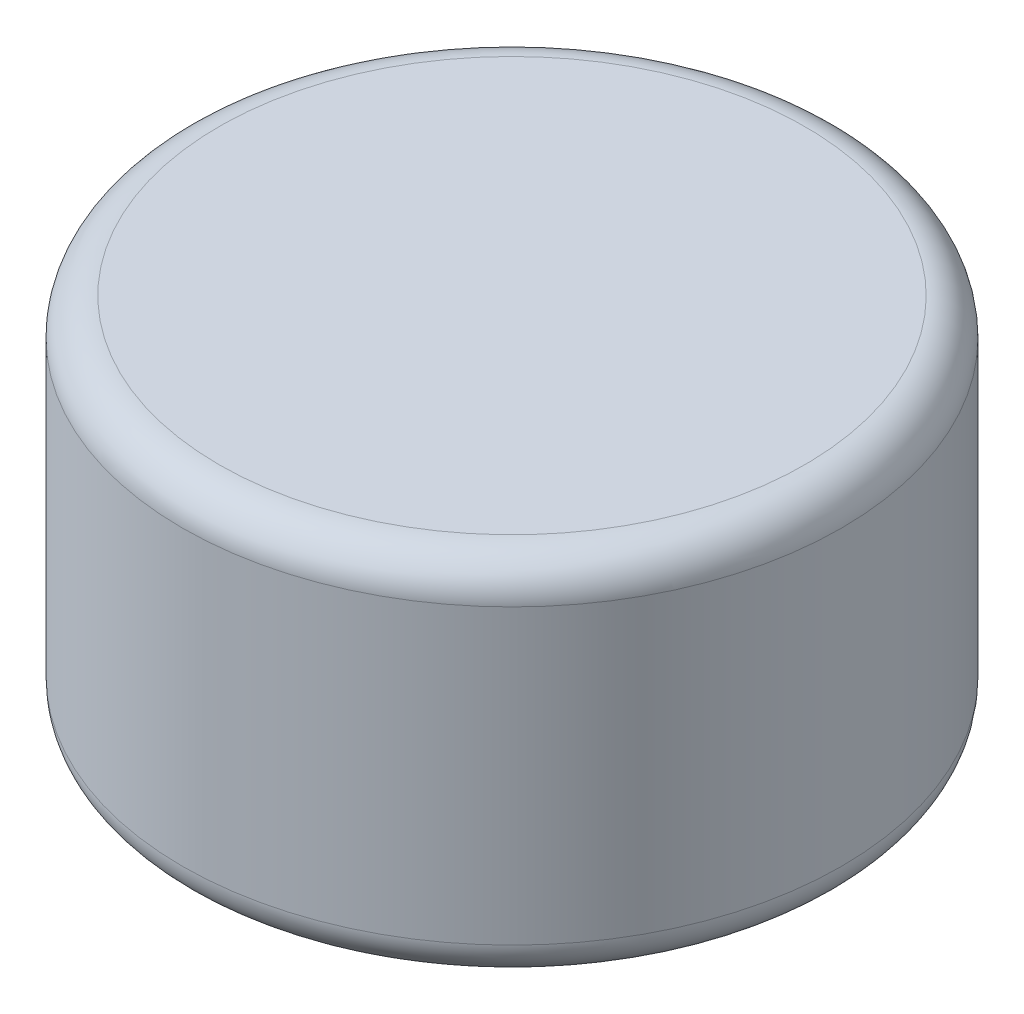
SolidWorks part; units mm, degrees
other "相机1"
other "相机2"
material "PEN"
ref_plane "前视基准面" through (0, 0, 0) normal (0, 0, 1) x (1, 0, 0)
ref_plane "上视基准面" through (0, 0, 0) normal (0, 1, 0) x (1, 0, 0)
ref_plane "右视基准面" through (0, 0, 0) normal (1, 0, 0) x (0, 0, -1)
sketch "草图1" plane through (0, 0, 0) normal (0, 1, 0) x (1, 0, 0)
  circle A0 centre (0, 0) radius 45
extrude "凸台-拉伸1" add sketch "草图1" along normal mid plane 50
fillet "圆角1" radius 5 2 edges at (0, -25, 45) (0, 25, 45)
sketch "草图9" plane through (0, 0, 0) normal (0, 1, 0) x (1, 0, 0)
  circle A0 centre (0, 0) radius 40.1
extrude "切除-拉伸1" cut sketch "草图9" against normal mid plane 40.1
